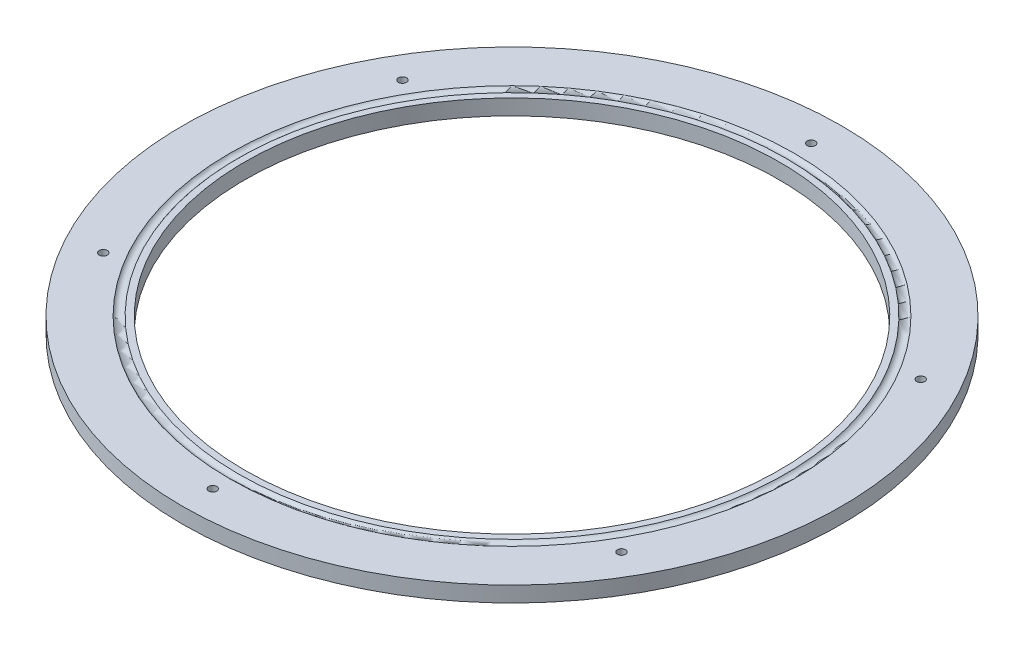
SolidWorks part; units mm, degrees
ref_plane "Front Plane" through (0, 0, 0) normal (0, 0, 1) x (1, 0, 0)
ref_plane "Top Plane" through (0, 0, 0) normal (0, 1, 0) x (1, 0, 0)
ref_plane "Right Plane" through (0, 0, 0) normal (1, 0, 0) x (0, 0, -1)
sketch "Sketch1" plane through (0, 0, 0) normal (0, 1, 0) x (1, 0, 0)
  circle A0 centre (0, 0) radius 87.3125
  circle A1 centre (0, 0) radius 101.2825
  circle A3 centre (0, 0) radius 94.2975
  circle A4 centre (0, -97.79) radius 1.3208
  circle A5 centre (0, 0) radius 107.7087
  dimension "D1" = 174.625
  dimension "D5" = 2.6416
  dimension "D6" = 215.4174
  dimension "D4" = 97.79
  dimension "D2" = 13.97
  dimension "D3" = 6.985
extrude "Boss-Extrude1" add sketch "Sketch1" along normal blind 5.08 contours A3 A0 | A1 A4 A3 | A5 A1 region at (-98.4178, 0, 0) region at (-91.6304, 0, 0) region at (-104.6622, 0, 0)
sketch "Sketch2" plane through (0, 0, 0) normal (1, 0, 0) x (0, 0, -1)
  line L0 (-87.3125, 0) -> (87.3125, 0) construction
  line L1 (87.3125, 5.08) -> (-87.3125, 5.08) construction
  line L2 (-87.3125, 0) -> (87.3125, 0)
  line L3 (87.3125, 5.08) -> (-87.3125, 5.08)
  line L4 (91.6697, 4.318) -> (97.1828, 4.318) construction
  line L5 (0, 5.08) -> (0, 35.8369)
  circle A0 centre (90.805, 5.9055) radius 1.5875 construction
  circle A1 centre (90.805, 5.969) radius 1.651
  dimension "D2" = 3.175
  dimension "D4" = 3.302
  dimension "D1" = 90.805
  dimension "D3" = 0.762
revolve "Cut-Revolve2" cut sketch "Sketch2" angle 360 about L5
pattern_circular "CirPattern1" count 6 over 360 about axis through (0, 5.08, 0) along (0, 1, 0) of face at (0, 5.08, 99.1108)
equation "\"Middle Coupler Inner Daimeter\"= 6.25in"
equation "\"Middle Coupler  Wall Thickness\" = 0.25in"
equation "\"Middle Coupler Bottom Thickness\"= 0.2in"
equation "\"Bearing Rail Offset\"= 0.45in"
equation "\"3-56 UNF Tap\"= 0.089in"
equation "\"3-56 UNF Clearance\"= 0.104in"
equation "\"Ball Bearing Distance\"= 0.03in"
equation "\"D1@Sketch1\"=\"Middle Coupler Inner Daimeter\"+0.625in"
equation "\"D3@Sketch1\"=\"D2@Sketch1\"/2"
equation "\"D4@Sketch1\"=(\"D1@Sketch1\"+\"D3@Sketch1\"+\"D2@Sketch1\")/2"
equation "\"D5@Sketch1\"=\"3-56 UNF Clearance\""
equation "\"D1@Sketch2\"=\"Middle Coupler Inner Daimeter\"/2in + \"Bearing Rail Offset\""
equation "\"D3@Sketch2\"=\"Ball Bearing Distance\""
equation "\"D4@Sketch2\"=\"D2@Sketch2\"+0.005"
equation "\"TCA Outer Diameter\" = 8.625in"
equation "\"D6@Sketch1\"=\"TCA Outer Diameter\"-0.144"
